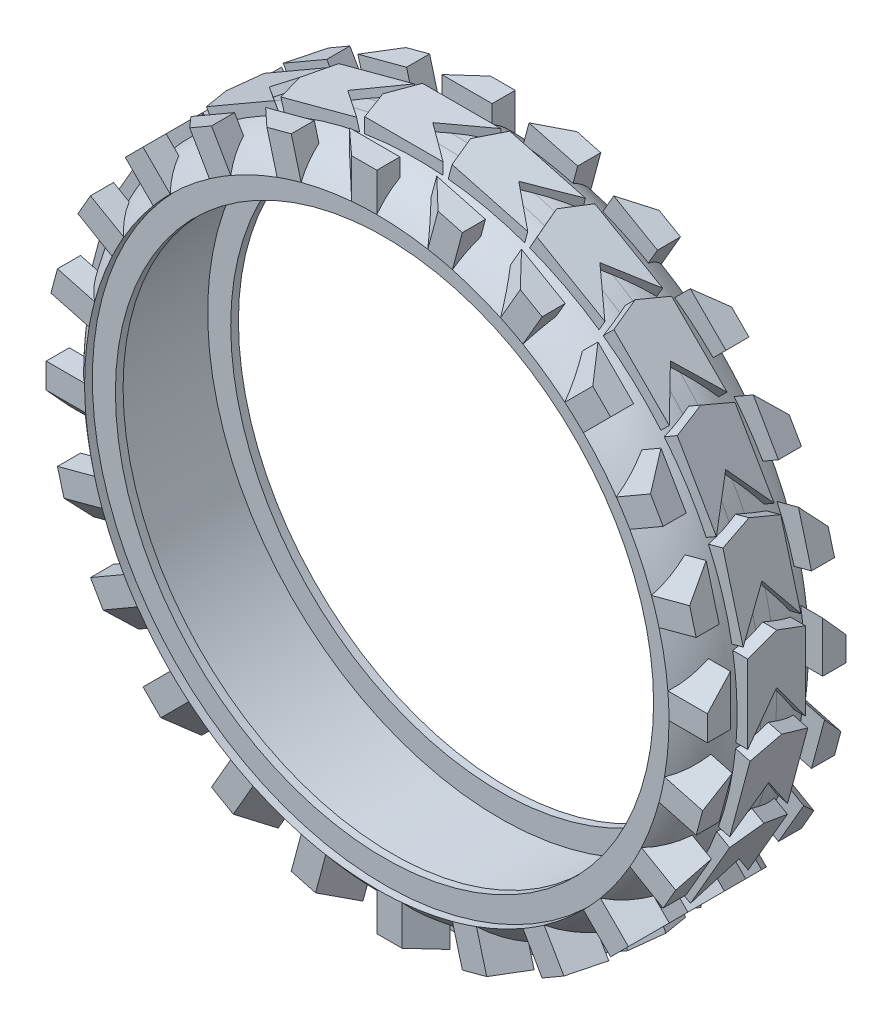
SolidWorks part; units mm, degrees
ref_plane "Front Plane" through (0, 0, 0) normal (0, 0, 1) x (1, 0, 0)
ref_plane "Top Plane" through (0, 0, 0) normal (0, 1, 0) x (1, 0, 0)
ref_plane "Right Plane" through (0, 0, 0) normal (1, 0, 0) x (0, 0, -1)
sketch "Sketch2" plane through (0, 0, 0) normal (1, 0, 0) x (0, 0, -1)
  line L0 (0, 0) -> (0, 42) construction
  line L1 (-9, 42) -> (9, 42)
  line L2 (9, 42) -> (9, 38)
  line L3 (-9, 42) -> (-9, 38)
  line L4 (9, 38) -> (8.5, 38)
  line L5 (-9, 38) -> (-8.5, 38)
  line L6 (8, 35.5) -> (8, 35)
  line L7 (-8, 37.5) -> (-8, 35)
  line L8 (8, 35) -> (7, 35)
  line L9 (-11.9819, 0) -> (11.9819, 0)
  line L10 (7, 35) -> (7, 38)
  line L11 (7, 38) -> (0, 38)
  line L12 (0, 38) -> (-7, 38)
  line L13 (-7, 38) -> (-7, 35)
  line L14 (-7, 35) -> (-8, 35)
  line L17 (-8.5, 38) -> (-8, 38)
  line L18 (-8, 38) -> (-8, 37.5)
  line L19 (8, 35.5) -> (8, 38)
  line L20 (8, 38) -> (8.5, 38)
  point P11 (0, 31)
  point P15 (0, 0)
  point P22 (-8, 38)
  point P25 (8, 38)
  dimension "D1" = 42
  dimension "D2" = 18
  dimension "D3" = 4
  dimension "D4" = 1
  dimension "D5" = 3
  dimension "D6" = 1
  dimension "D7" = 1
revolve "Revolve2" add sketch "Sketch2" angle 360 about L9 region at (0, 39.7308, 0)
fillet "Fillet1" radius 10 2 edges at (42, 0, 9) (42, 0, -9)
ref_plane "Plane1" through (43, 0, 0) normal (1, 0, 0) x (0, 0, -1)
sketch "Sketch3" plane through (43, 0, 0) normal (1, 0, 0) x (0, 0, -1)
  line L6 (-6.0009, 6.5534) -> (-9, 3.2767)
  line L10 (-9, 38) -> (-9, -38) construction
  line L11 (0, 8.2091) -> (3.756, 6.8124)
  line L12 (-6.0009, 6.5534) -> (-6.0009, 0)
  line L13 (-6.0009, 0) -> (-9, 0)
  line L14 (-9, 0) -> (-9, 3.2767)
  line L15 (0, 46.2) -> (0, -46.2) construction
  line L16 (6.0009, 0) -> (9, 0)
  line L17 (6.0009, 6.5534) -> (6.0009, 0)
  line L18 (9, 0) -> (9, 3.197)
  line L20 (0, 8.2091) -> (-3.756, 6.8124)
  line L21 (3.756, 6.8124) -> (3.756, -3.3743)
  line L22 (-3.756, 6.8124) -> (-3.756, -3.3743)
  line L23 (3.756, -3.3743) -> (0, 1.719)
  line L24 (-3.756, -3.3743) -> (0, 1.719)
  line L25 (6.0009, 6.5534) -> (9, 3.197)
  point P3 (0, 3.197)
  point P18 (0, 3.197)
  dimension "D1" = 7.5119
extrude "Boss-Extrude1" add sketch "Sketch3" against normal up to next contours L14 L13 L12 | L18 L17 L16 | L23 L24 L22 L20 L11 L21 region at (43, 2.5485, 7.3338) region at (43, 2.5339, -7.3284)
sketch "Sketch6" plane through (0, 0, 0) normal (1, 0, 0) x (0, 0, -1)
  line L0 (0, 0) -> (50.4312, 0)
pattern_circular "CirPattern1" count 24 over 360 about axis through (0, 0, 0) along (0, 0, -1) of "Boss-Extrude1"
